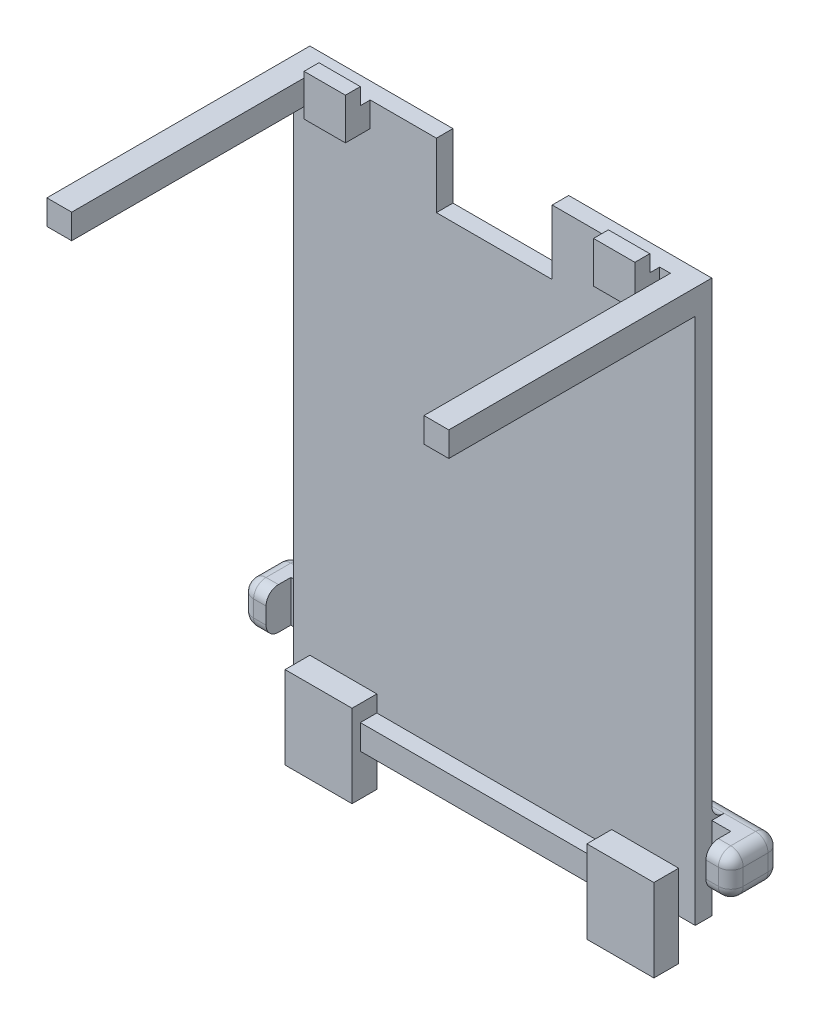
SolidWorks part; units mm, degrees
ref_plane "前视基准面" through (0, 0, 0) normal (0, 0, 1) x (1, 0, 0)
ref_plane "上视基准面" through (0, 0, 0) normal (0, 1, 0) x (1, 0, 0)
ref_plane "右视基准面" through (0, 0, 0) normal (1, 0, 0) x (0, 0, -1)
other "Configuration Table"
sketch "草图1" plane through (0, 0, -32) normal (0, 0, -1) x (-1, 0, 0)
  line L0 (-41, 12) -> (12, 12) construction
  line L1 (-38.8, 78.8) -> (9.8, 78.8)
  line L2 (-38.8, 78.8) -> (-38.8, 12)
  line L3 (-38.8, 12) -> (9.8, 12)
  line L4 (9.8, 78.8) -> (9.8, 12)
  line L5 (-39, 12) -> (-39, 82) construction
  line L6 (10, 79) -> (10, 12) construction
  line L10 (-39, 79) -> (-23, 79) construction
  dimension "D1" = 0.2
  dimension "D2" = 0.2
  dimension "D3" = 0.2
extrude "凸台-拉伸1" add sketch "草图1" against normal up to surface (2 mm away)
sketch "草图2" plane through (0, 0, -30) normal (0, 0, 1) x (1, 0, 0)
  line L0 (-8, 17) -> (-8, 12) construction
  line L1 (-7.8, 17) -> (0.3, 17)
  line L2 (-7.8, 17) -> (-7.8, 7)
  line L3 (-7.8, 7) -> (0.3, 7)
  line L4 (0.3, 17) -> (0.3, 7)
  line L5 (38.8, 12) -> (-9.8, 12) construction
  line L6 (0.5, 12) -> (0.5, 6) construction
  dimension "D1" = 0.2
  dimension "D2" = 10
  dimension "D3" = 5
  dimension "D4" = 0.2
extrude "凸台-拉伸2" add sketch "草图2" along normal blind 3
ref_plane "基准面1" through (14.5, 0, 0) normal (-1, 0, 0) x (0, 0, 1)
mirror "镜向1" about plane through (14.5, 0, 0) normal (-1, 0, 0) of "凸台-拉伸2"
sketch "草图3" plane through (0, 0, -30) normal (0, 0, 1) x (1, 0, 0)
  line L0 (-12, 12) -> (41, 12) construction
  line L1 (0.3, 15) -> (28.7, 15)
  line L2 (0.3, 15) -> (0.3, 12)
  line L3 (0.3, 12) -> (28.7, 12)
  line L4 (28.7, 15) -> (28.7, 12)
  line L6 (0.3, 12) -> (0.3, 17) construction
  line L7 (28.7, 12) -> (28.7, 17) construction
  dimension "D1" = 3
extrude "凸台-拉伸3" add sketch "草图3" along normal blind 2
sketch "草图4" plane through (0, 0, -32) normal (0, 0, -1) x (-1, 0, 0)
  line L0 (-14.5, 78.8) -> (-14.5, 33.7688) construction
  line L1 (9.8, 78.8) -> (-38.8, 78.8) construction
  line L3 (-21.5, 79) -> (-7.5, 79)
  line L4 (-21.5, 79) -> (-21.5, 71)
  line L5 (-21.5, 71) -> (-7.5, 71)
  line L6 (-7.5, 79) -> (-7.5, 71)
  line L7 (-39, 79) -> (-23, 79) construction
  dimension "D1" = 8
extrude "切除-拉伸1" cut sketch "草图4" against normal through all
sketch "草图5" plane through (0, 0, -30) normal (0, 0, 1) x (1, 0, 0)
  line L0 (14.5, 71) -> (14.5, 35.8876) construction
  line L1 (7.5, 71) -> (21.5, 71) construction
  line L2 (-9.8, 78.8) -> (7.5, 78.8) construction
  line L3 (-5.5, 80.8) -> (-0.5, 80.8)
  line L4 (-5.5, 80.8) -> (-5.5, 75.8)
  line L5 (-5.5, 75.8) -> (-0.5, 75.8)
  line L6 (-0.5, 80.8) -> (-0.5, 75.8)
  line L7 (29.5, 80.8) -> (29.5, 75.8)
  line L8 (34.5, 75.8) -> (29.5, 75.8)
  line L9 (34.5, 80.8) -> (34.5, 75.8)
  line L10 (34.5, 80.8) -> (29.5, 80.8)
  dimension "D1" = 2
  dimension "D2" = 5
  dimension "D3" = 5
  dimension "D4" = 15
extrude "凸台-拉伸4" add sketch "草图5" along normal blind 3
sketch "草图6" plane through (0, 80.8, 0) normal (0, 1, 0) x (1, 0, 0)
  line L0 (-0.5, 30) -> (-5.5, 30) construction
  line L1 (-5.5, 30) -> (-0.5, 30)
  line L2 (-5.5, 30) -> (-5.5, 28.8)
  line L3 (-5.5, 28.8) -> (-0.5, 28.8)
  line L4 (-0.5, 30) -> (-0.5, 28.8)
  line L6 (-5.5, 27) -> (-5.5, 30) construction
  line L7 (-0.5, 27) -> (-0.5, 30) construction
  line L8 (14.5, 32) -> (14.5, 4.8493) construction
  line L10 (29.5, 30) -> (29.5, 28.8)
  line L11 (34.5, 28.8) -> (29.5, 28.8)
  line L12 (34.5, 30) -> (34.5, 28.8)
  line L13 (34.5, 30) -> (29.5, 30)
  line L14 (-10, 29) -> (39, 29) construction
  line L15 (41, 32) -> (-12, 32) construction
  point P14 (14.5, 32)
  dimension "D1" = 0.2
extrude "切除-拉伸2" cut sketch "草图6" against normal up to surface (2 mm away) up to face at (-1.7667, 78.8, -30.6667)
sketch "草图7" plane through (0, 0, -30) normal (0, 0, 1) x (1, 0, 0)
  line L0 (14.5, 71) -> (14.5, 61.8228) construction
  line L1 (-9.8, 78.8) -> (-6.8, 78.8)
  line L2 (-9.8, 78.8) -> (-9.8, 75.8)
  line L3 (-9.8, 75.8) -> (-6.8, 75.8)
  line L4 (-6.8, 78.8) -> (-6.8, 75.8)
  line L5 (7.5, 71) -> (21.5, 71) construction
  line L6 (35.8, 78.8) -> (35.8, 75.8)
  line L7 (38.8, 75.8) -> (35.8, 75.8)
  line L8 (38.8, 78.8) -> (38.8, 75.8)
  line L9 (38.8, 78.8) -> (35.8, 78.8)
  dimension "D1" = 3
  dimension "D2" = 3
extrude "凸台-拉伸5" add sketch "草图7" along normal offset from surface (29.8 mm away) 0.2
sketch "草图8" plane through (0, 0, -32) normal (0, 0, -1) x (-1, 0, 0)
  line L1 (4.8, 22) -> (15.1, 22)
  line L2 (4.8, 22) -> (4.8, 17)
  line L3 (4.8, 17) -> (15.1, 17)
  line L4 (15.1, 22) -> (15.1, 17)
  line L5 (9.8, 12) -> (9.8, 78.8) construction
  line L6 (-41, 12) -> (12, 12) construction
  line L8 (12, 12) -> (12, 85) construction
  dimension "D1" = 5
  dimension "D2" = 5
  dimension "D3" = 3.1
  dimension "D4" = 5
extrude "凸台-拉伸6" add sketch "草图8" along normal blind 3
sketch "草图9" plane through (0, 0, -32) normal (0, 0, 1) x (1, 0, 0)
  line L0 (-15.1, 22) -> (-9.8, 22) construction
  line L1 (-15.1, 22) -> (-12.1, 22)
  line L2 (-15.1, 22) -> (-15.1, 17)
  line L3 (-15.1, 17) -> (-12.1, 17)
  line L4 (-12.1, 22) -> (-12.1, 17)
  line L5 (-15.1, 17) -> (-15.1, 22) construction
  line L7 (-9.8, 17) -> (-15.1, 17) construction
  line L8 (-12, 12) -> (-12, 85) construction
  dimension "D1" = 0.1
extrude "凸台-拉伸7" add sketch "草图9" along normal blind 3
fillet "圆角1" radius 1.5 12 edges at (-15.1, 19.5, -29) (-15.1, 22, -32) (-15.1, 17, -32) (-4.8, 19.5, -32) (-7.3, 17, -32) (-9.95, 17, -35) (-4.8, 19.5, -35) (-7.3, 22, -32) (-9.95, 22, -35) (-15.1, 19.5, -35) (-13.6, 22, -29) (-13.6, 17, -29)
ref_plane "基准面2" through (14.5, 0, 0) normal (-1, 0, 0) x (0, 0, 1)
mirror "镜向2" about plane through (14.5, 0, 0) normal (-1, 0, 0) of "圆角1", "凸台-拉伸7", "凸台-拉伸6"
